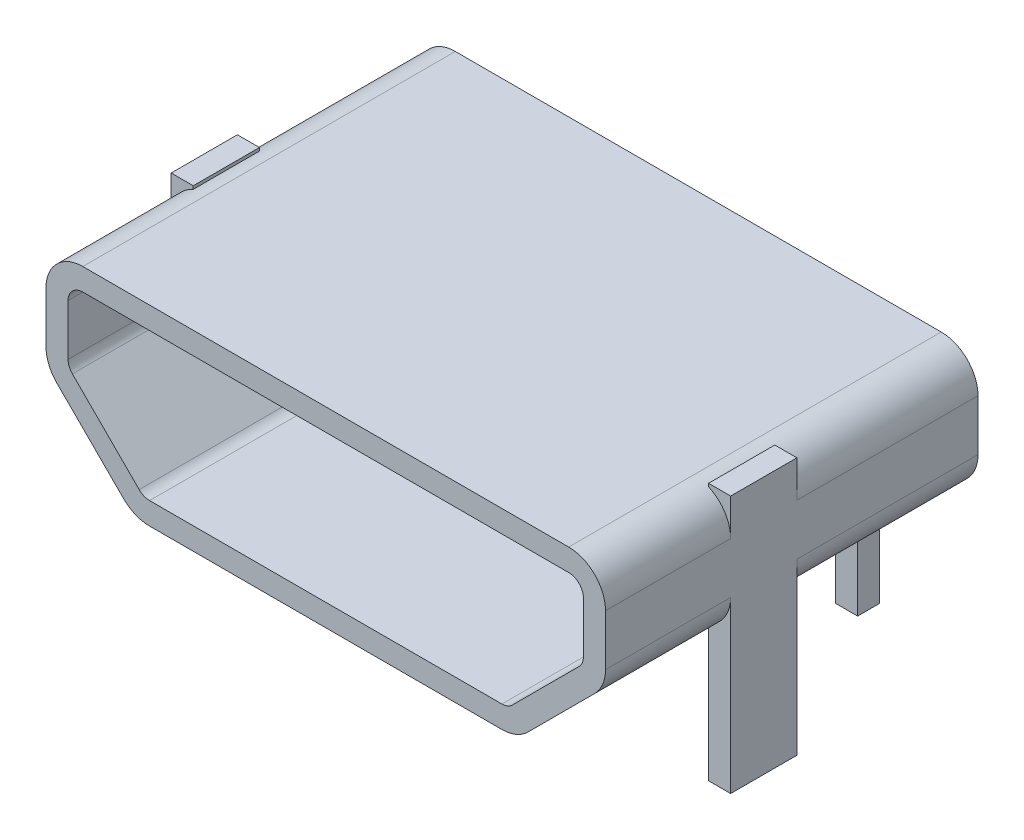
SolidWorks part; units mm, degrees
ref_plane "前视基准面" through (0, 0, 0) normal (0, 0, 1) x (1, 0, 0)
ref_plane "上视基准面" through (0, 0, 0) normal (0, 1, 0) x (1, 0, 0)
ref_plane "右视基准面" through (0, 0, 0) normal (1, 0, 0) x (0, 0, -1)
sketch "草图1" plane through (0, 0, 0) normal (0, 0, 1) x (1, 0, 0)
  line L0 (-3.6536, 1.0536) -> (-2.7464, 0.1464)
  line L1 (-2.3929, 0) -> (2.3929, 0)
  line L2 (-3.8, 1.4071) -> (-3.8, 2.1)
  line L3 (-3.3, 2.6) -> (3.3, 2.6)
  line L4 (3.8, 1.4071) -> (3.8, 2.1)
  line L5 (2.7464, 0.1464) -> (3.6536, 1.0536)
  arc A0 (3.6536, 1.0536) -> (3.8, 1.4071) centre (3.3, 1.4071) ccw
  arc A1 (2.7464, 0.1464) -> (2.3929, 0) centre (2.3929, 0.5) cw
  arc A2 (-3.6536, 1.0536) -> (-3.8, 1.4071) centre (-3.3, 1.4071) cw
  arc A3 (-2.7464, 0.1464) -> (-2.3929, 0) centre (-2.3929, 0.5) ccw
  arc A4 (-3.8, 2.1) -> (-3.3, 2.6) centre (-3.3, 2.1) cw
  arc A5 (3.3, 2.6) -> (3.8, 2.1) centre (3.3, 2.1) cw
  point P0 (-3.8, 0)
  point P3 (3.8, 0)
  point P10 (0, 0)
  point P14 (3.8, 1.2)
  point P17 (2.6, 0)
  point P20 (-3.8, 1.2)
  point P23 (-2.6, 0)
  dimension "D3" = 0.5
  dimension "D4" = 0.5
  dimension "D7" = 0.5
  dimension "D8" = 0.5
  dimension "D9" = 0.5
  dimension "D10" = 0.5
  dimension "D1" = 2.6
  dimension "D2" = 7.6
extrude "凸台-拉伸1" add sketch "草图1" along normal blind 5.06
sketch "草图4" plane through (0, 0, 0) normal (0, 0, -1) x (-1, 0, 0)
  line L8 (-2.3929, 0.3) -> (2.3929, 0.3)
  line L9 (-3.5, 2.1) -> (-3.5, 1.4071)
  line L10 (3.3, 2.3) -> (-3.3, 2.3)
  line L11 (3.5, 1.4071) -> (3.5, 2.1)
  line L12 (-2.3929, 0.3) -> (2.3929, 0.3)
  line L13 (-3.5, 2.1) -> (-3.5, 1.4071)
  line L14 (3.3, 2.3) -> (-3.3, 2.3)
  line L15 (3.5, 1.4071) -> (3.5, 2.1)
  line L18 (-3.4414, 1.2657) -> (-2.5343, 0.3586)
  line L19 (-3.4414, 1.2657) -> (-2.5343, 0.3586)
  line L20 (2.5343, 0.3586) -> (3.4414, 1.2657)
  line L21 (2.5343, 0.3586) -> (3.4414, 1.2657)
  arc A6 (-2.5343, 0.3586) -> (-2.3929, 0.3) centre (-2.3929, 0.5) ccw
  arc A7 (-2.5343, 0.3586) -> (-2.3929, 0.3) centre (-2.3929, 0.5) ccw
  arc A8 (-3.5, 1.4071) -> (-3.4414, 1.2657) centre (-3.3, 1.4071) ccw
  arc A9 (-3.5, 1.4071) -> (-3.4414, 1.2657) centre (-3.3, 1.4071) ccw
  arc A10 (-3.3, 2.3) -> (-3.5, 2.1) centre (-3.3, 2.1) ccw
  arc A11 (-3.3, 2.3) -> (-3.5, 2.1) centre (-3.3, 2.1) ccw
  arc A12 (3.5, 2.1) -> (3.3, 2.3) centre (3.3, 2.1) ccw
  arc A13 (3.5, 2.1) -> (3.3, 2.3) centre (3.3, 2.1) ccw
  arc A14 (3.4414, 1.2657) -> (3.5, 1.4071) centre (3.3, 1.4071) ccw
  arc A15 (3.4414, 1.2657) -> (3.5, 1.4071) centre (3.3, 1.4071) ccw
  arc A16 (2.3929, 0.3) -> (2.5343, 0.3586) centre (2.3929, 0.5) ccw
  arc A17 (2.3929, 0.3) -> (2.5343, 0.3586) centre (2.3929, 0.5) ccw
  dimension "D1" = 0.3
extrude "切除-拉伸1" cut sketch "草图4" against normal up to next
sketch "草图2" plane through (0, 2.6, 0) normal (0, 1, 0) x (1, 0, 0)
  line L0 (0, 0) -> (0, -50000) construction
  line L1 (-2.575, -0.11) -> (-2.275, -0.11)
  line L2 (-2.575, -0.11) -> (-2.575, -0.41)
  line L3 (-2.575, -0.41) -> (-2.275, -0.41)
  line L4 (-2.275, -0.11) -> (-2.275, -0.41)
  line L5 (-2.575, -0.11) -> (-2.275, -0.41) construction
  line L6 (-2.575, -0.41) -> (-2.275, -0.11) construction
  line L7 (-3.8, -5.06) -> (-3.8, 0) construction
  line L8 (-3.8, -3.36) -> (-3.5, -3.36)
  line L9 (-3.8, -3.36) -> (-3.8, -2.46)
  line L10 (-3.8, -2.46) -> (-3.5, -2.46)
  line L11 (-3.5, -3.36) -> (-3.5, -2.46)
  line L12 (-3.8, -3.36) -> (-3.5, -2.46) construction
  line L13 (-3.8, -2.46) -> (-3.5, -3.36) construction
  line L14 (3.8, -2.46) -> (3.5, -3.36) construction
  line L15 (3.8, -3.36) -> (3.5, -2.46) construction
  line L16 (2.575, -0.41) -> (2.275, -0.11) construction
  line L17 (2.575, -0.11) -> (2.275, -0.41) construction
  line L18 (3.5, -3.36) -> (3.5, -2.46)
  line L19 (3.8, -2.46) -> (3.5, -2.46)
  line L20 (3.8, -3.36) -> (3.8, -2.46)
  line L21 (3.8, -3.36) -> (3.5, -3.36)
  line L22 (2.275, -0.11) -> (2.275, -0.41)
  line L23 (2.575, -0.41) -> (2.275, -0.41)
  line L24 (2.575, -0.11) -> (2.575, -0.41)
  line L25 (2.575, -0.11) -> (2.275, -0.11)
  line L26 (3.3, -5.06) -> (-3.3, -5.06) construction
  point P4 (-2.425, -0.26)
  point P12 (-3.65, -2.91)
  point P23 (3.65, -2.91)
  point P24 (2.425, -0.26)
  dimension "D1" = 0.3
  dimension "D2" = 0.3
  dimension "D3" = 0.3
  dimension "D4" = 0.9
  dimension "D5" = 4.85
  dimension "D6" = 4.8
  dimension "D7" = 2.6
extrude "凸台-拉伸2" add sketch "草图2" against normal blind 3.5
